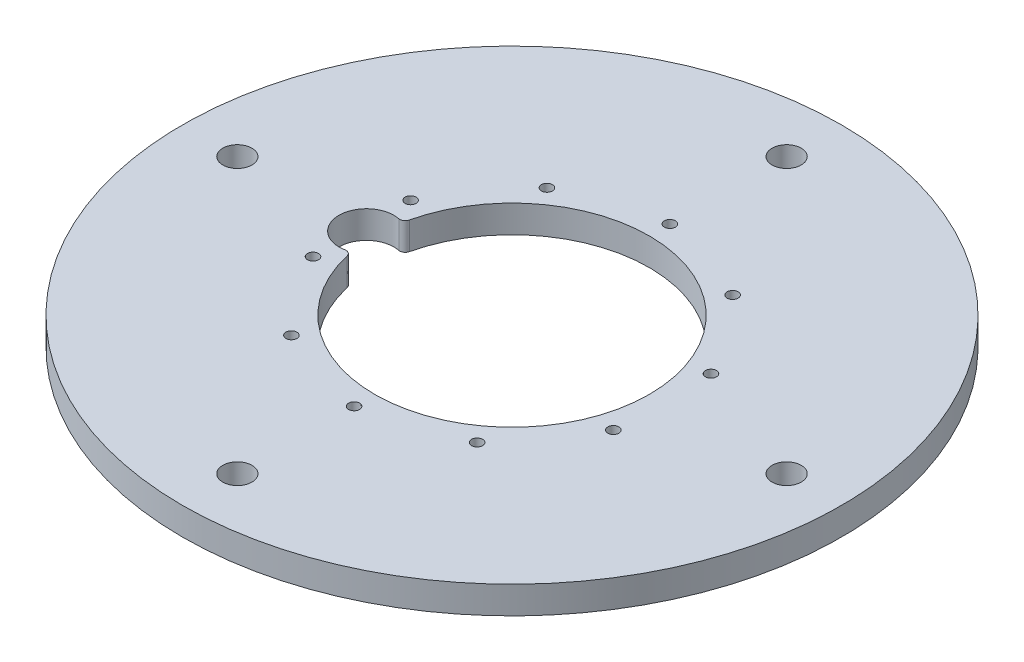
SolidWorks part; units mm, degrees
material "6061 Alloy"
ref_plane "Front Plane" through (0, 0, 0) normal (0, 0, 1) x (1, 0, 0)
ref_plane "Top Plane" through (0, 0, 0) normal (0, 1, 0) x (1, 0, 0)
ref_plane "Right Plane" through (0, 0, 0) normal (1, 0, 0) x (0, 0, -1)
sketch "Sketch1" plane through (0, 0, 0) normal (0, 1, 0) x (1, 0, 0)
  line L1 (0, 0) -> (0, 73.025) construction
  line L2 (0, 0) -> (0, 127) construction
  circle A3 centre (0, 0) radius 152.4
  circle A8 centre (0, 0) radius 127 construction
  circle A20 centre (0, 0) radius 63.5
  circle A23 centre (0, 0) radius 73.025 construction
  point P0 (0, 163.8008)
  point P2 (0, 127)
  point P5 (0, 73.025)
  dimension "Diameter_Takeout_BoltCircle" = 254
  dimension "Diameter_ThrustPlate" = 304.8
  dimension "D2" = 146.05
  dimension "D4" = 127
  dimension "D1" = 0
extrude "ThrustPlate_TC3" add sketch "Sketch1" against normal blind 12.7 separate body contours A3 region at (-148.0895, 0, 0)
sketch "Sketch11" plane through (0, 0, 0) normal (0, 1, 0) x (1, 0, 0)
  point P0 (0, 127)
hole_wizard "UNDEF_Clearance_ThrustPlate" positions "Sketch11" profile "Sketch12" hole size "1/2" standard "ANSI Inch" end condition through all
sketch "Sketch12" plane through (0, 0, -127) normal (1, 0, 0) x (0, 0, 1)
  line L0 (0, 0) -> (0, 12.7)
  line L1 (0, 12.7) -> (6.7462, 12.7)
  line L2 (6.7462, 12.7) -> (6.7462, 0)
  line L5 (6.7462, 0) -> (0, 0)
  line L11 (0, -6.35) -> (0, 107.95) construction
  dimension "Thru Hole Dia." = 13.4925
  dimension "Thru Hole Depth" = 12.7
pattern_circular "Clearance_ThrustPlate_Pattern" count 4 over 360 about axis through (0, -12.7, 0) along (0, 1, 0) of "UNDEF_Clearance_ThrustPlate" reverse direction yes
sketch "Sketch22" plane through (0, 0, 0) normal (0, 1, 0) x (1, 0, 0)
  point P0 (0, 73.025)
  point P3 (0, 0)
hole_wizard "#10 Clearance Hole1" positions "Sketch22" profile "Sketch23" hole size "#10" standard "ANSI Inch" end condition through all
sketch "Sketch23" plane through (0, 0, -73.025) normal (1, 0, 0) x (0, 0, 1)
  line L0 (0, 0) -> (0, 12.7)
  line L1 (0, 12.7) -> (2.5527, 12.7)
  line L2 (2.5527, 12.7) -> (2.5527, 0)
  line L5 (2.5527, 0) -> (0, 0)
  line L11 (0, -6.35) -> (0, 107.95) construction
  dimension "Thru Hole Dia." = 5.1054
  dimension "Thru Hole Depth" = 12.7
pattern_circular "CirPattern1" count 10 over 360 about axis through (0, -12.7, 0) along (0, 1, 0) of "#10 Clearance Hole1" reverse direction yes
sketch "Sketch24" plane through (0, 0, 0) normal (0, 1, 0) x (1, 0, 0)
  line L0 (0, 0) -> (0, 152.4) construction
  line L1 (0, 0) -> (-152.4, 0) construction
  circle A0 centre (0, 0) radius 152.4 construction
  circle A1 centre (0, 0) radius 63.5 construction
  arc A3 (-64.8239, 12.4543) -> (-64.8239, -12.4543) centre (-67.31, 0) ccw
  arc A6 (-64.8239, 12.4543) -> (-61.8526, 14.3703) centre (-64.3267, 14.9452) ccw
  arc A7 (-61.8526, 14.3703) -> (-61.8526, -14.3703) centre (0, 0) ccw
  arc A8 (-64.8239, -12.4543) -> (-61.8526, -14.3703) centre (-64.3267, -14.9452) cw
  point P13 (-49.9469, 39.2118)
  point P14 (-53.4346, 38.6445)
  point P15 (-51.6107, 36.9945)
  dimension "D2" = 12.7
  dimension "D4" = 2.54
  dimension "D1" = 67.31
  dimension "D3" = 90
extrude "Cut-Extrude1" cut sketch "Sketch24" against normal up to next
equation "\"Diameter_BackPlate\"= 6"
equation "\"VAR_Diameter_BackPlate_BoltCircle\"= 5.75"
equation "\"VAR_Diameter_FuelOuterPlenum\"= 4.4"
equation "\"Thickness_ThrustPlate\"= 0.5'undetermined"
equation "\"Diameter_ThrustPlate\"= 12'defined"
equation "\"Diameter_Takeout_BoltCicle\"= 10'defined"
equation "\"Diameter_Takeout_BoltCircle@Sketch1\"=\"Diameter_Takeout_BoltCicle\""
equation "\"Diameter_ThrustPlate@Sketch1\"=\"Diameter_ThrustPlate\""
equation "\"D1@ThrustPlate_TC3\"=\"Thickness_ThrustPlate\""
equation "\"VAR_Diameter_CBORE\"= 0.44'undetermined"
equation "\"VAR_Diameter_Clearance_ThrustPlate\"= 0.25'undetermined"
equation "\"NumberBolts_BackPlate\"= 20"
equation "\"NumberBolts_Takeout\"= 4'defined"
equation "\"D1@Clearance_ThrustPlate_Pattern\"=\"NumberBolts_Takeout\""
